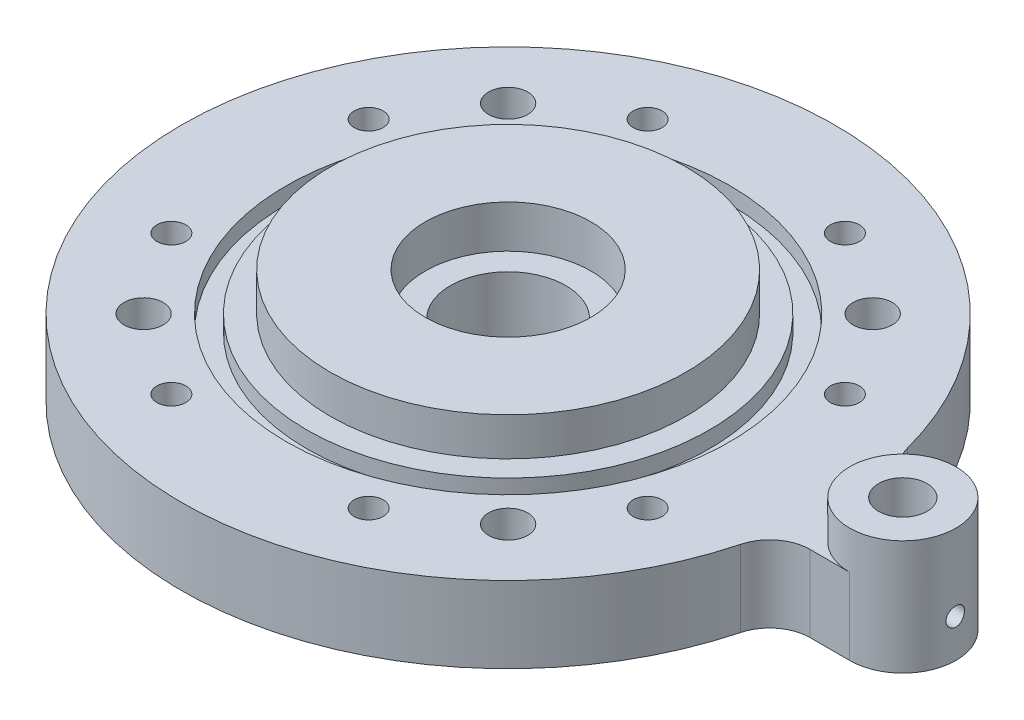
SolidWorks part; units mm, degrees
material "1060 Alloy"
ref_plane "Front" through (0, 0, 0) normal (0, 0, 1) x (1, 0, 0)
ref_plane "Top" through (0, 0, 0) normal (0, 1, 0) x (1, 0, 0)
ref_plane "Right" through (0, 0, 0) normal (1, 0, 0) x (0, 0, -1)
sketch "Sketch1" plane through (0, 0, 0) normal (0, 1, 0) x (1, 0, 0)
  line L0 (58.8962, 0) -> (68.0634, 0) construction
  line L1 (61.2588, 9.1672) -> (68.0634, 9.1672)
  line L2 (61.2588, -9.1672) -> (68.0634, -9.1672)
  line L3 (58.8962, 0) -> (77.2306, 0) construction
  line L4 (58.8962, 0) -> (56.3562, 0) construction
  arc A0 (54.4905, 14.3809) -> (54.4905, -14.3809) centre (0, 0) ccw
  circle A1 centre (0, 0) radius 56.3562 construction
  arc A2 (68.0634, -9.1672) -> (68.0634, 9.1672) centre (68.0634, 0) ccw
  arc A3 (54.4905, 14.3809) -> (61.2588, 9.1672) centre (61.2588, 16.1672) ccw
  arc A4 (61.2588, -9.1672) -> (54.4905, -14.3809) centre (61.2588, -16.1672) ccw
  point P5 (34.5422, 0)
  point P10 (55.6057, 9.1672)
  dimension "D1" = 112.7125
  dimension "D4" = 7
  dimension "D2" = 18.3344
  dimension "D3" = 18.3344
  dimension "D5" = 2.54
extrude "base" add sketch "Sketch1" along normal blind 13.175
sketch "Sketch2" plane through (0, 13.175, 0) normal (0, 1, 0) x (1, 0, 0)
  line L0 (68.0634, 9.1672) -> (68.0634, -9.1672) construction
  circle A0 centre (0, 0) radius 30.6705
  arc A1 (68.0634, -9.1672) -> (68.0634, 9.1672) centre (68.0634, 0) ccw construction
  circle A2 centre (68.0634, 0) radius 9.1672
  circle A3 centre (68.0634, 0) radius 4.1672
  dimension "D1" = 61.341
  dimension "D2" = 8.3344
sketch "Sketch3" plane through (0, 0, 0) normal (0, -1, 0) x (1, 0, 0)
  line L0 (0, 0) -> (77.2306, 0) construction
  line L1 (0, 0) -> (39.8499, -39.8499) construction
  circle A0 centre (0, 0) radius 44.45 construction
  circle A1 centre (-31.4309, -31.4309) radius 3.3734
  circle A2 centre (-31.4309, 31.4309) radius 3.3734
  circle A3 centre (31.4309, 31.4309) radius 3.3734
  circle A4 centre (31.4309, -31.4309) radius 3.3734
  arc A5 (68.0634, -9.1672) -> (68.0634, 9.1672) centre (68.0634, 0) ccw construction
  arc A6 (54.4905, 14.3809) -> (54.4905, -14.3809) centre (0, 0) ccw construction
  point P14 (0, 0)
  dimension "D1" = 88.9
  dimension "D2" = 6.7469
  dimension "D4" = 45
  dimension "D3" = 4
extrude "square bolt holes" cut sketch "Sketch3" against normal through all
sketch "Sketch4" plane through (0, 13.175, 0) normal (0, 1, 0) x (1, 0, 0)
  line L0 (0, 0) -> (0, 44.45) construction
  line L1 (0, 44.45) -> (0, 0) construction
  line L2 (0, 0) -> (17.0103, 41.0664) construction
  circle A0 centre (0, 0) radius 44.45 construction
  circle A1 centre (17.0103, 41.0664) radius 2.5
  dimension "D1" = 88.9
  dimension "D3" = 5
  dimension "D2" = 22.5
extrude "housing bolts" cut sketch "Sketch4" against normal blind 44.33
pattern_circular "CirPattern1" count 8 over 360 about axis through (0, 13.175, 0) along (0, 1, 0) of "housing bolts"
extrude "impeller cavity riser" add sketch "Sketch2" along normal blind 6.59
sketch "Sketch5" plane through (0, 19.765, 0) normal (0, 1, 0) x (1, 0, 0)
  circle A0 centre (0, 0) radius 14.2875
  dimension "D1" = 28.575
extrude "seal bore" cut sketch "Sketch5" against normal blind 7.35
sketch "Sketch6" plane through (0, 12.415, 0) normal (0, 1, 0) x (1, 0, 0)
  circle A0 centre (0, 0) radius 9.9375
  dimension "D1" = 19.875
extrude "bore" cut sketch "Sketch6" against normal blind 39.3
sketch "pressure tap plane alignment" plane through (0, 0, 0) normal (0, -1, 0) x (1, 0, 0)
  line L1 (0, 0) -> (56.3562, 0) construction
  line L2 (56.3562, 0) -> (56.3562, 56.3563) construction
  line L3 (56.3562, 56.3563) -> (0, 56.3562) construction
  circle A0 centre (0, 0) radius 56.3562 construction
  circle A1 centre (0, 0) radius 56.3562 construction
ref_plane "pressure tap plane" through (56.3562, 0, 0) normal (1, 0, 0) x (0, 0, -1)
sketch "Sketch9" plane through (56.3562, 0, 0) normal (1, 0, 0) x (0, 0, -1)
  line L0 (0, 0) -> (0, 13.175) construction
  line L1 (56.3562, 13.175) -> (-56.3563, 13.175) construction
  circle A0 centre (0, 6.5875) radius 1.5875
  dimension "D1" = 3.175
extrude "pressure tap" cut sketch "Sketch9" against normal blind 56.3562 and the other way through all
sketch "Sketch10" plane through (0, 13.175, 0) normal (0, 1, 0) x (1, 0, 0)
  circle A0 centre (68.0634, 0) radius 1.5875
  dimension "D1" = 3.175
extrude "pressure tap vertical hole" cut sketch "Sketch10" against normal blind 8.175
sketch "Sketch12" plane through (0, 13.175, 0) normal (0, 1, 0) x (1, 0, 0)
  circle A0 centre (0, 0) radius 34.7218
  circle A1 centre (0, 0) radius 38.2524
  dimension "D1" = 76.5048
  dimension "D2" = 69.4436
extrude "Cut-Extrude1" cut sketch "Sketch12" against normal blind 2.8245
equation "\"de\" = 0.43in\t\t\t'entrance eye diameter"
equation "\"d2\" = 2.1in \t\t\t'outer diameter of the impeller"
equation "\"d_exit\" = 0.18in \t\t'throat aka d1"
equation "\"theta\" = 12\t\t\t'angle of blades from inner to outer "
equation "\"impeller upper clearance\"= .5mm"
equation "\"impeller horizontal clearance\"= (\"d2\"*1.15 - \"d2\")/2 \t\t'clearance based on D2-D3 ratio for circular volute, ranges 1.15 to 1.2"
equation "\"impeller bottom clearance\"= .5mm"
equation "\"impeller base thickness\"= 2mm"
equation "\"impeller dowel diameter\" = 2mm"
equation "\"impeller bolt head diameter\" = \"m4 head bore diameter\""
equation "\"impeller bolt head depth\" = 4mm"
equation "\"impeller bolt stop depth\" = 3mm"
equation "\"impeller bolt bore\" = \"m4 clearance\""
equation "\"impeller shaft bore depth\" = 12mm"
equation "\"impeller shaft bore\" = 8mm"
equation "\"impeller boss depth\" = \"impeller shaft bore depth\"+\"impeller bolt stop depth\"+\"impeller bolt head depth\"-\"impeller base thickness\""
equation "\"impeller boss diameter\" = \"upper seal ID\""
equation "\"impeller dowel length\" = 2mm*2 + \"impeller shaft bore\""
equation "\"coupler motor shaft hole ID\"= 8mm"
equation "\"coupler OD\"= 17mm"
equation "\"coupler length\"= 25mm"
equation "\"motor OD\" = 64mm"
equation "\"motor shaft diameter\"= 8mm"
equation "\"motor shaft pride\"= 32mm"
equation "\"motor to bearing plate distance\" = \"motor shaft pride\" + 2mm +\"coupler length\"/2"
equation "\"square plate bolt bore\" = \"m8 clearance\""
equation "\"square plate bolt head diameter\" = 13.5mm"
equation "\"square plate bolt pattern diameter\"= 3.5in"
equation "\"motor mount center bore\"= \"coupler OD\"+ 4mm"
equation "\"motor mount post radius\"= ( 3 * \"square plate bolt bore\" ) / 2"
equation "\"motor mount m4 screw hole diameter\"= 4mm"
equation "\"motor mount m4 head diameter\"= 7.25mm"
equation "\"motor mount m4 head depth\"= 4mm"
equation "\"motor mount m4 pattern diamater\" = 30mm"
equation "\"motor mount plate thickness\"= 8mm + \"motor mount m4 head depth\""
equation "\"shaft coupler section diameter\" = 8mm"
equation "\"shaft coupler section length\" = \"motor to bearing plate distance\" - \"motor shaft pride\" - 2mm"
equation "\"shaft bearing section diameter\" = \"bearing ID\""
equation "\"shaft bearing section length\" = \"bearing plate stop depth\" + \"bearing depth\""
equation "\"shaft bearing stop diameter\" = \"bearing ID\" + 4mm"
equation "\"shaft bearing stop length\" = 3mm"
equation "\"impeller cavity center height\"= \"impeller bottom clearance\" + \"impeller upper clearance\" + \"impeller center height\""
equation "\"impeller cavity diameter\"= 2 * \"impeller horizontal clearance\" + \"d2\" \t\t\t\t\t\t\t\t\t'called D3 analytically"
equation "\"impeller cavity outer height\"= \"impeller bottom clearance\" + \"impeller upper clearance\" + \"impeller base thickness\" + \"b2\" \t\t'this is height at impeller diameter d2, not at d3"
equation "\"impeller housing thickness\"= \"impeller housing exit threaded diameter\" + 2*\"impeller housing outlet grip\""
equation "\"impeller housing diameter\" = \"square plate bolt pattern diameter\" + 2*\"motor mount post radius\""
equation "\"impeller housing bolt count\" = 8"
equation "\"impeller housing bolt diameter\" = \"m6 clearance\""
equation "\"impeller housing bolt pattern diameter\" = 3.5in"
equation "\"impeller housing threaded inlet diameter\" = 0.515625in \t'this is the 33/64 drill size for 9/16-18 fitting, expecting swagelok SS-8FK0-1-6STH fitting"
equation "\"impeller housing threaded inlet depth\"= 10mm"
equation "\"impeller housing exit threaded diameter\"= 0.515625in \t\t'this is the 33/64 drill size for 9/16-18 fitting, expecting swagelok SS-8FK0-1-6STH fitting"
equation "\"impeller housing exit threaded depth\"= 10mm"
equation "\"impeller housing diffuser conical angle\"=10"
equation "\"impeller housing diffuser tangent angle\"=5"
equation "\"impeller housing outlet grip\" = 5mm"
equation "\"D1@Sketch1\"=\"impeller housing diameter\""
equation "\"D1@base\" = \"upper seal plate thickness\""
equation "\"D1@Sketch2\"=\"impeller cavity diameter\""
equation "\"D1@Sketch3\"=\"square plate bolt pattern diameter\""
equation "\"D2@Sketch3\"=\"m8 tap\""
equation "\"D1\" = \"upper seal plate thickness\" - 2mm"
equation "\"D1@Sketch4\"=\"impeller housing bolt pattern diameter\""
equation "\"D2@Sketch4\"=360/\"impeller housing bolt count\"/2"
equation "\"D3@Sketch4\"=\"m6 tap\""
equation "\"D1@CirPattern1\"=\"impeller housing bolt count\""
equation "\"D1@impeller cavity riser\" = \"upper seal plate riser\""
equation "\"D1@Sketch5\" = \"upper seal OD\""
equation "\"D1@seal bore\" = \"upper seal bore\""
equation "\"D1@Sketch6\" = \"upper seal ID\" + 4mm"
equation "\"D1@Sketch9\" = \"upper seal plate pressure hole diameter\""
equation "\"D1@pressure tap\"=\"impeller housing diameter\"/2"
equation "\"de_length\" = 10mm\t\t'entrance eye consistent length"
equation "\"square plate bolt head depth\" = 8mm"
equation "\"shaft impeller section diameter\" = \"impeller shaft bore\""
equation "\"shaft impeller section length\" = \"upper seal plate thickness\" + \"upper seal plate riser\" + \"impeller bottom clearance\" + \"impeller base thickness\" - \"impeller bolt head depth\" - \"impeller bolt stop depth\""
equation "\"impeller housing diffuser final diameter\" = .38in\t\t'aka d2'"
equation "\"D2@Sketch1\" = \"upper seal plate pressure tap diameter\" + \"upper seal plate pressure tap grip\" * 2"
equation "\"D3@Sketch1\" = \"upper seal plate pressure tap diameter\" + \"upper seal plate pressure tap grip\" * 2"
equation "\"D2@pressure tap\"=\"big seal plate pressure tap diameter\"/2+\"big seal plate pressure tap grip\""
equation "\"D2@Sketch2\" = \"upper seal plate pressure tap diameter\""
equation "\"D1@Sketch10\" = \"upper seal plate pressure hole diameter\""
equation "\"D1@pressure tap vertical hole\"= \"upper seal plate thickness\" / 2 + \"upper seal plate pressure hole diameter\" / 2"
equation "\"end mill size\" = 0.375in\t'for 3/8 endmill"
equation "\"m6 clearance\" = 0.234375in\t'this is 15/64 bit = 5.95mm, could use 6mm bit, B bit for 6.04mm or 1/4 bit for 6.35mm"
equation "\"m6 tap\" = 5mm\t\t\t'5mm is appropriate, could use 13/64 or #5,6,7"
equation "\"m6 head bore diameter\" = 11mm\t\t"
equation "\"m6 head bore depth\" = 7mm\t'actual is 6mm"
equation "\"m8 clearance\" = 0.3125in\t'this is 5/16in for 7.93mm, could use 8mm, O,P, or 21/64"
equation "\"m8 tap\" = 0.265625in\t\t'this is 17/64 for 6.746875mm"
equation "\"m8 head bore diameter\" = 14mm"
equation "\"m8 head bore depth\" = 9mm\t'actual is 8mm"
equation "\"ce\" = 3.14*\"de\"\t\t'entrance eye circumference"
equation "\"s_open\" = \"av\"/\"b1\"\t\t'width of open area"
equation "\"impeller center height\" = \"impeller base thickness\" + \"b1\"\t'impeller height at de"
equation "\"impeller outer height\" = \"impeller base thickness\" + \"b2\"\t'impeller height at de"
equation "\"lower seal OD\" = .917in\t\t'this is https://www.mcmaster.com/#9281k121/=174001b"
equation "\"lower seal ID\"= .375in"
equation "\"lower seal depth\" = .625in + .218in"
equation "\"lower seal bore\" = \"lower seal depth\" + 1mm"
equation "\"upper seal OD\" = 1.125in\t'this is https://www.mcmaster.com/#5154t33/=173zuau, needs to be visually inspected before machining!"
equation "\"upper seal ID\"= 0.625in"
equation "\"upper seal depth\"= .25in\t'aka height; these values need to be confirmed by inspection!! We may want to compress the height."
equation "\"upper seal bore\" = \"upper seal depth\" + 1mm"
equation "\"lower seal plate lip depth\" = 2mm"
equation "\"lower seal plate lip ID\" = \"lower seal OD\" - 3mm"
equation "\"lower seal plate thickness\" = \"lower seal plate lip depth\" + \"lower seal bore\""
equation "\"shaft lower seal section diameter\" = \"lower seal ID\""
equation "\"shaft lower seal section length\" = \"lower seal plate thickness\" + 1mm"
equation "\"upper seal plate thickness\" = \"upper seal plate pressure hole diameter\"+10mm"
equation "\"upper seal plate lip ID\" = \"upper seal OD\" - 3mm"
equation "\"upper seal plate riser\" = 6.59mm \t\t'this number needs to be read from the housing file"
equation "\"upper seal plate pressure hole diameter\" = .125in\t'this is 1/8 drill "
equation "\"upper seal plate pressure tap diameter\" = .328125in \t'this is 21/64 drill for a 1/8 ANPT tap"
equation "\"upper seal plate pressure tap grip\" = 5mm\t\t'this is the area around the tap so it doesn't crack"
equation "\"upper seal plate pressure tap depth\" = 12"
equation "\"bearing OD\" = 30mm"
equation "\"bearing ID\"= 10mm"
equation "\"bearing depth\"= 9mm"
equation "\"bearing outer race thickness\"= 1mm"
equation "\"bearing inner race thickness\"= 1mm"
equation "\"bearing bore\" = \"bearing depth\" + 1mm"
equation "\"z\" = 8\t\t\t\t'number of blades"
equation "\"b2\" = .2in\t\t\t'tip height from disc surface at d2; slightly higher than d_exit"
equation "\"b1\" = \"b2\" + (\"d2\"/2 - \"de\"/2)*tan(\"theta\") \t\t\t'tip height from disc surface at inlet eye"
equation "\"ae\" = 3.14*(\"de\"^2)/4\t\t'entrance eye area'"
equation "\"av_ratio\" = .325\t\t'ratio of av/ae at N_s of 470, range is .275 to .375, .325 ideal. High ratio means bigger area means smaller blades"
equation "\"av\" = \"ae\"*\"av_ratio\"\t\t'area between just two blades"
equation "\"s\"=\"ce\" - \"z\"*\"s_open\""
equation "\"bearing plate stop ID\" = \"bearing OD\" - 4mm"
equation "\"bearing plate stop depth\" = 3mm"
equation "\"bearing plate thickness\" = \"bearing bore\" + \"bearing plate stop depth\" + \"shaft bearing stop length\""
equation "\"m4 clearance\" = 0.171875in \t'this is 11/64 bit for 4.36mm"
equation "\"m4 tap\" = 0.125in\t\t'this is 1/8 bit for 3.17mm"
equation "\"m4 head bore diameter\" = 7.5mm"
equation "\"m4 head bore depth\" = 5mm\t'actual is ~4mm"
equation "\"big o-ring thickness\" = .139in"
equation "\"big o-ring OD\" = 2.734in"
equation "\"big o-ring ID\" = 3.012in"
equation "\"big o-ring groove depth\" = \"big o-ring thickness\"*4/5"
equation "\"D1@Sketch12\"=\"big o-ring ID\""
equation "\"D2@Sketch12\"=\"big o-ring OD\""
equation "\"D1@Cut-Extrude1\"=\"big o-ring groove depth\""
equation "\"min blade thickness\" = .15in"
